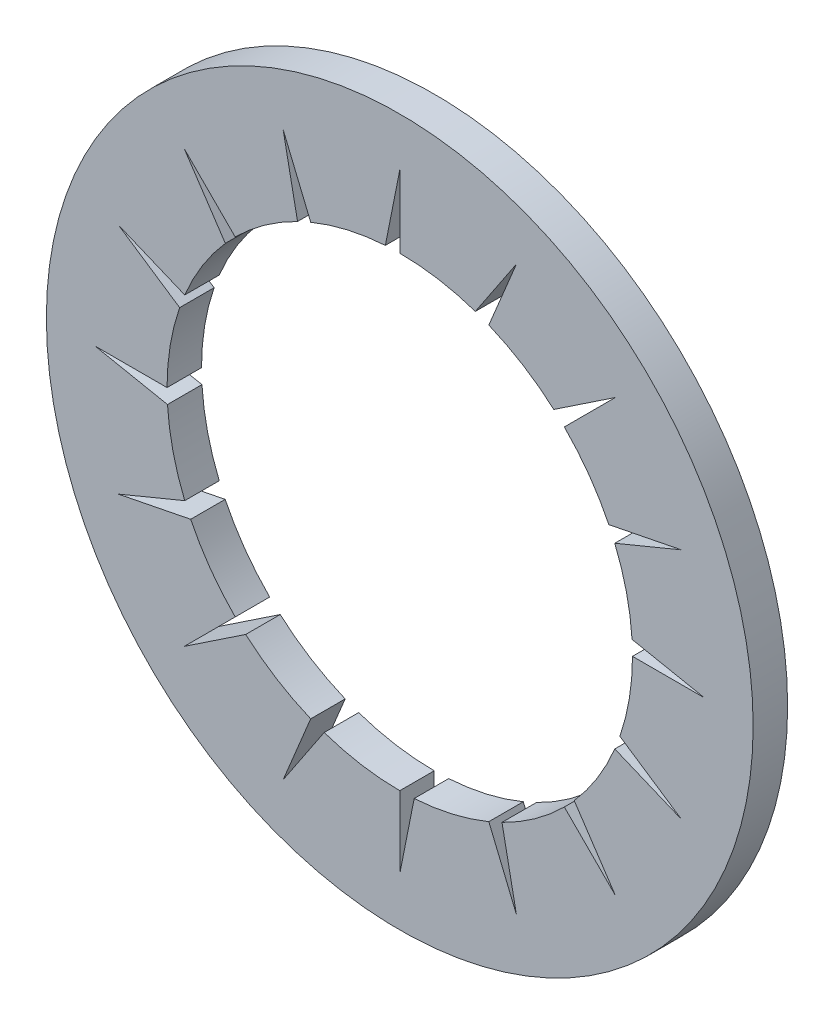
SolidWorks part; units mm, degrees
ref_plane "Front Plane" through (0, 0, 0) normal (0, 0, 1) x (1, 0, 0)
ref_plane "Top Plane" through (0, 0, 0) normal (0, 1, 0) x (1, 0, 0)
ref_plane "Right Plane" through (0, 0, 0) normal (1, 0, 0) x (0, 0, -1)
sketch "BodySke" plane through (0, 0, 0) normal (0, 1, 0) x (1, 0, 0)
  line L0 (0, 0) -> (0, 16) construction
  line L2 (6.75, 0) -> (10.25, 0)
  line L3 (6.75, 0) -> (6.75, 1)
  line L4 (6.75, 1) -> (10.25, 1)
  line L5 (10.25, 0) -> (10.25, 1)
revolve "BaseBody" add sketch "BodySke" angle 360 about L0
sketch "ToothSke" plane through (0, 0, 0) normal (0, 0, 1) x (1, 0, 0)
  line L0 (0, 0) -> (0, 2.7341) construction
  line L1 (0, 8.84) -> (-0.4183, 6.737)
  line L3 (0, 6.75) -> (0, 8.84)
  circle A0 centre (0, 0) radius 8.84 construction
  arc A1 (-0.7581, 8.8074) -> (0.7581, 8.8074) centre (0, 0) cw construction
  circle A2 centre (0, 0) radius 6.75 construction
  arc A3 (0, 6.75) -> (-0.4183, 6.737) centre (0, 0) ccw
  dimension "D1" = 17.68
  dimension "D2" = 11.25
extrude "ToothCut" cut sketch "ToothSke" against normal through all
pattern_circular "ToothPat" count 16 over 360 about axis through (0, 0, 0) along (0, 0, -1) of "ToothCut"
equation "\"D1@ToothSke\" =  ( \"Inner_dia@BodySke\" + \"Outer_dia@BodySke\" )  * 0.52"
equation "\"Num_tooth@ToothPat\" = \"Num_tooth@BodySke\""
equation "\"D2@ToothSke\" = 180 / \"Num_tooth@BodySke\""
